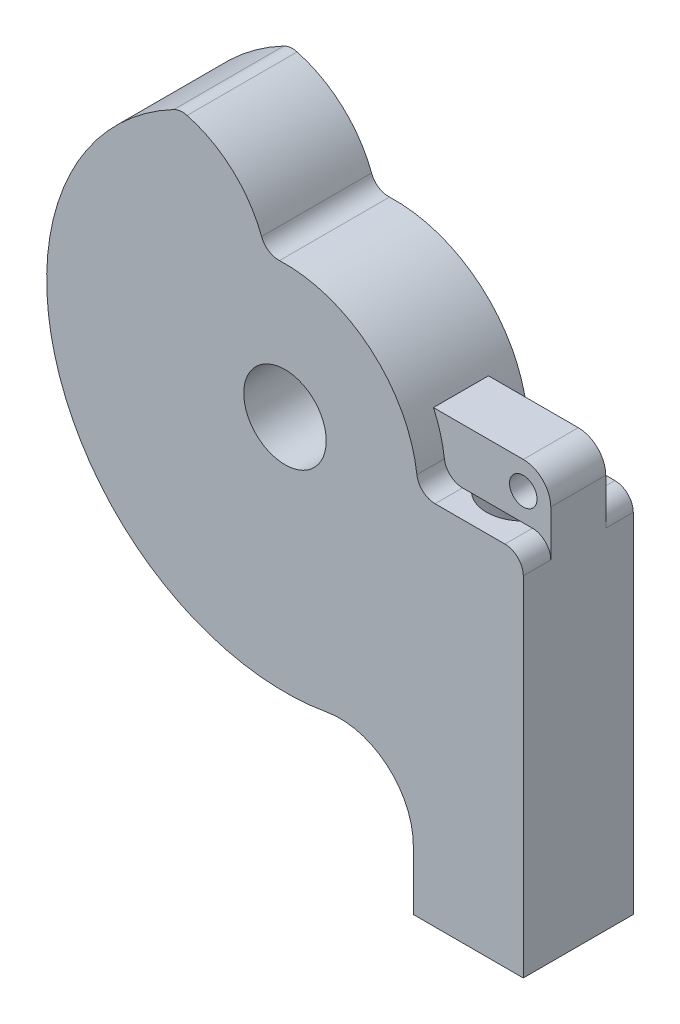
SolidWorks part; units mm, degrees
ref_plane "Front Plane" through (0, 0, 0) normal (0, 0, 1) x (1, 0, 0)
ref_plane "Top Plane" through (0, 0, 0) normal (0, 1, 0) x (1, 0, 0)
ref_plane "Right Plane" through (0, 0, 0) normal (1, 0, 0) x (0, 0, -1)
sketch "Sketch2" plane through (0, 0, 0) normal (0, 0, 1) x (1, 0, 0)
  line L0 (13, 0) -> (13, -20)
  line L1 (13, -20) -> (7, -20)
  line L2 (7, -20) -> (7, -10.9545)
  line L3 (10, 0) -> (10, -20) construction
  arc A0 (13, 0) -> (7, -10.9545) centre (0, 0) ccw
  circle A1 centre (0, 0) radius 10 construction
  dimension "Diameter" = 20
  dimension "Rod Holer Thickness" = 6
  dimension "Rod Holder Length" = 20
extrude "Boss-Extrude1" add sketch "Sketch2" along normal mid plane 6
hole_wizard "M4 Clearance Hole1" positions "Sketch3" profile "Sketch4" hole size "M4" standard "ANSI Metric" end condition up to next
sketch "Sketch3" plane through (0, 0, 3) normal (0, 0, 1) x (1, 0, 0)
  point P2 (0, 0)
sketch "Sketch4" plane through (0, 0, 3) normal (1, 0, 0) x (0, -1, 0)
  line L0 (0, 0) -> (0, 6)
  line L1 (0, 6) -> (2.25, 6)
  line L2 (2.25, 6) -> (2.25, 0)
  line L5 (2.25, 0) -> (0, 0)
  line L11 (0, -6.35) -> (0, 107.95) construction
  dimension "Thru Hole Dia." = 4.5
  dimension "Thru Hole Depth" = 6
sketch "Sketch5" plane through (0, -20, 0) normal (0, -1, 0) x (1, 0, 0)
  line L0 (13, 3) -> (7, -3) construction
  circle A0 centre (10, 0) radius 2
  dimension "Rod Hole Diameter" = 4
extrude "Cut-Extrude1" cut sketch "Sketch5" against normal blind 20
ref_axis "Axis1" through (10, 0, 0) along (0, -1, 0)
sketch "Sketch8" plane through (0, 0, -3) normal (0, 0, 1) x (1, 0, 0)
  line L0 (0, 0) -> (-21.8723, 0) construction
  line L1 (0, 0) -> (-6.8944, 5.7851) construction
  circle A0 centre (-6.8944, 5.7851) radius 3
  dimension "D2" = 6
  dimension "D1" = 40
  dimension "D3" = 9
extrude "Cut-Extrude3" cut sketch "Sketch8" along normal offset from surface (4.4 mm away) 1.6 up to face at (2.25, 0, 3)
sketch "Sketch9" plane through (0, 0, 3) normal (0, 0, 1) x (1, 0, 0)
  line L1 (13, 0) -> (7.25, 0)
  line L2 (13, 0) -> (13, 10.075) construction
  arc A0 (13, 0) -> (7, -10.9545) centre (0, 0) ccw construction
  arc A1 (7.25, 0) -> (-1.057, 7.1725) centre (0, 0) ccw
  circle A2 centre (0, 0) radius 2.25 construction
  arc A4 (-1.057, 7.1725) -> (-5.7272, 11.6705) centre (-6.8944, 5.7851) ccw
  circle A5 centre (-6.8944, 5.7851) radius 3 construction
  arc A6 (13, 0) -> (-5.7272, 11.6705) centre (0, 0) ccw
  dimension "D1" = 5
  dimension "D2" = 3
extrude "Cut-Extrude4" cut sketch "Sketch9" against normal through all
sketch "Sketch6" plane through (0, 0, 0) normal (0, 0, 1) x (1, 0, 0)
  line L4 (13, 1.5) -> (13, 0)
  line L6 (11.5, 3) -> (6.6002, 3)
  line L8 (7.25, 0) -> (13, 0) construction
  line L9 (7.25, 0) -> (13, 0)
  arc A2 (13, 1.5) -> (11.5, 3) centre (11.5, 1.5) ccw
  arc A3 (7.25, 0) -> (-1.057, 7.1725) centre (0, 0) ccw construction
  arc A4 (7.25, 0) -> (6.6002, 3) centre (0, 0) ccw
  dimension "Spring Attchment Diameter" = 1.5
extrude "Boss-Extrude2" add sketch "Sketch6" along normal mid plane 3
fillet "Fillet1" radius 1 6 edges at (-5.7272, 11.6705, 0) (7.25, 0, 2.25) (7.25, 0, -2.25) (-1.057, 7.1725, 0) (13, 0, -2.25) (13, 0, 2.25)
sketch "Sketch7" plane through (0, 0, 1.5) normal (0, 0, 1) x (1, 0, 0)
  circle A0 centre (11.5, 1.5) radius 0.75
  arc A1 (13, 1.5) -> (11.5, 3) centre (11.5, 1.5) ccw construction
  dimension "Spring Hole Diam" = 1.5
extrude "Cut-Extrude2" cut sketch "Sketch7" against normal through all both and the other way through all
fillet "Fillet2" radius 4 1 edges at (7, -10.9545, 0)
